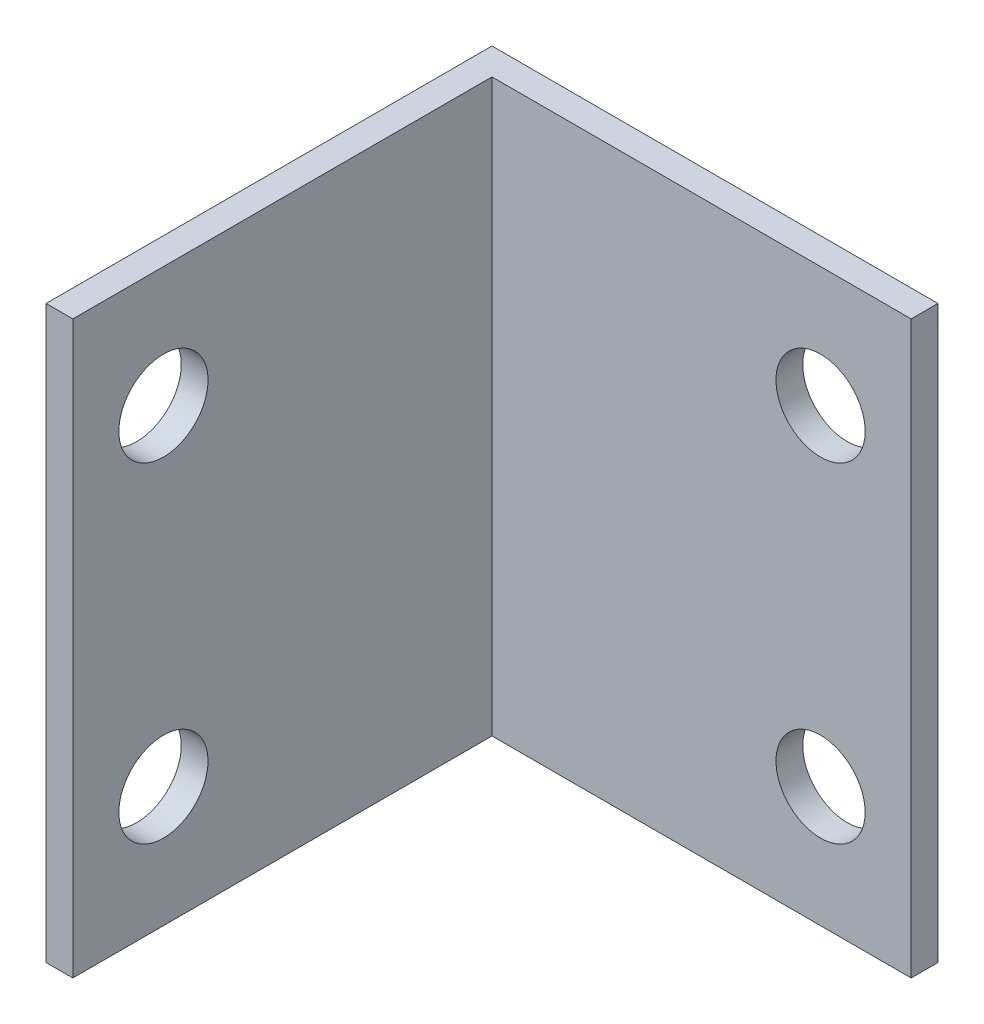
SolidWorks part; units mm, degrees
ref_plane "Front Plane" through (0, 0, 0) normal (0, 0, 1) x (1, 0, 0)
ref_plane "Top Plane" through (0, 0, 0) normal (0, 1, 0) x (1, 0, 0)
ref_plane "Right Plane" through (0, 0, 0) normal (1, 0, 0) x (0, 0, -1)
sketch "Sketch1" plane through (0, 0, 0) normal (0, 0, 1) x (1, 0, 0)
  line L0 (12.5, 0) -> (-12.5, 0) construction
  line L1 (-12.5, 16) -> (12.5, 16) construction
  line L2 (-12.5, 16) -> (-12.5, -16) construction
  line L3 (-12.5, -16) -> (12.5, -16) construction
  line L4 (12.5, 16) -> (12.5, -16) construction
  line L5 (-12.5, 16) -> (12.5, -16) construction
  line L6 (-12.5, -16) -> (12.5, 16) construction
  line L8 (-12.5, 16) -> (-12.5, -16)
  line L9 (-12.5, -16) -> (12.5, -16)
  line L10 (-12.5, 16) -> (12.5, 16)
  line L11 (12.5, 16) -> (12.5, -16)
  line L12 (7.42, 9.25) -> (7.42, -9.25) construction
  circle A3 centre (7.42, -9.25) radius 2.5
  circle A4 centre (7.42, 9.25) radius 2.5
  point P7 (0, 0)
  point P10 (7.42, 0)
  dimension "D1" = 18.5
  dimension "D4" = 5
  dimension "D5" = 5
  dimension "D2" = 25
  dimension "D3" = 32
  dimension "D6" = 5.08
extrude "Boss-Extrude1" add sketch "Sketch1" along normal blind 1.5
sketch "Sketch2" plane through (-12.5, 0, 0) normal (-1, 0, 0) x (0, 0, 1)
  line L0 (1.5, 16) -> (0, 16) construction
  line L1 (0, -16) -> (25, -16)
  line L2 (0, -16) -> (0, 16)
  line L3 (0, 16) -> (25, 16)
  line L4 (25, -16) -> (25, 16)
  line L5 (0, -16) -> (25, 16) construction
  line L6 (0, 16) -> (25, -16) construction
  line L7 (25, 0) -> (0, 0) construction
  line L8 (19.92, -9.25) -> (19.92, 9.25) construction
  circle A0 centre (19.92, -9.25) radius 2.5
  circle A1 centre (19.92, 9.25) radius 2.5
  point P4 (12.5, 0)
  point P12 (19.92, 0)
  dimension "D4" = 5
  dimension "D5" = 5
  dimension "D1" = 25
  dimension "D2" = 18.5
  dimension "D3" = 5.08
extrude "Boss-Extrude2" add sketch "Sketch2" against normal blind 1.5
